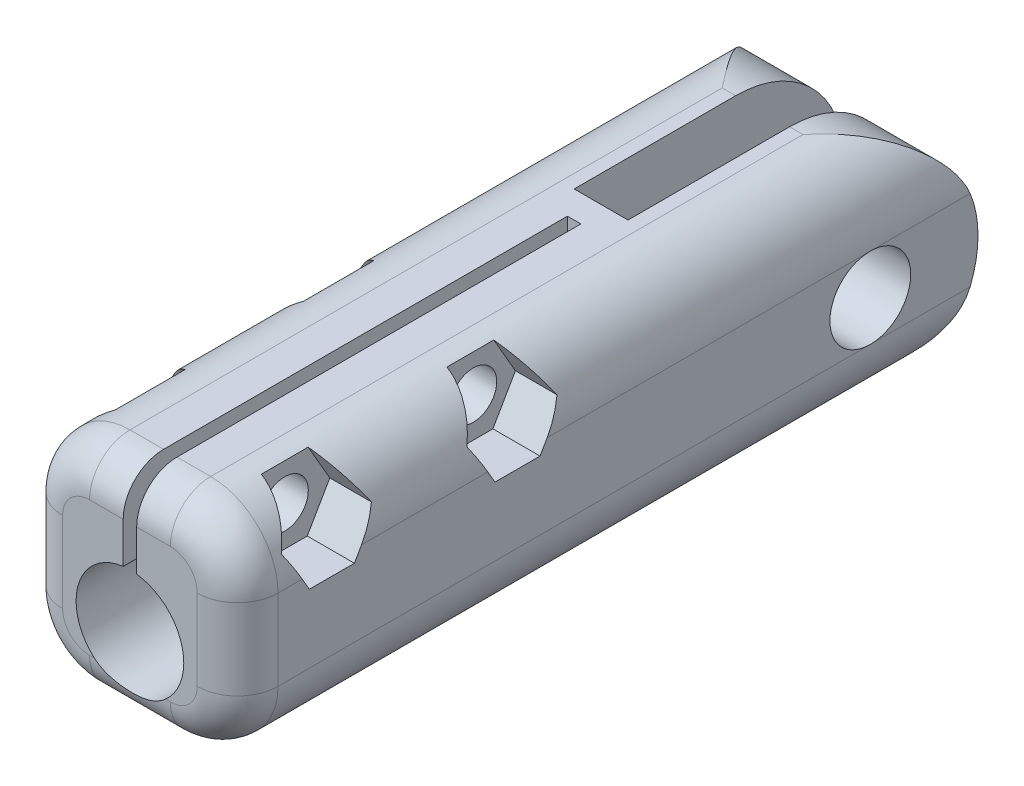
SolidWorks part; units mm, degrees
ref_plane "Front Plane" through (0, 0, 0) normal (0, 0, 1) x (1, 0, 0)
ref_plane "Top Plane" through (0, 0, 0) normal (0, 1, 0) x (1, 0, 0)
ref_plane "Right Plane" through (0, 0, 0) normal (1, 0, 0) x (0, 0, -1)
sketch "Sketch1" plane through (0, 0, 0) normal (0, 0, 1) x (1, 0, 0)
  line L1 (-8, -8) -> (8, -8)
  line L2 (-8, -8) -> (-8, 8)
  line L3 (-8, 8) -> (8, 8)
  line L4 (8, -8) -> (8, 8)
  line L5 (-8, -8) -> (8, 8) construction
  line L6 (-8, 8) -> (8, -8) construction
  point P0 (0, 0)
  dimension "D1" = 16
  dimension "D2" = 16
extrude "Boss-Extrude1" add sketch "Sketch1" along normal blind 55
sketch "Sketch2" plane through (0, 8, 0) normal (0, 1, 0) x (1, 0, 0)
  line L0 (0, 0) -> (0, -55) construction
  line L1 (8, 0) -> (-8, 0) construction
  line L2 (8, -55) -> (-8, -55) construction
  line L4 (2, -17) -> (-2, -17)
  line L5 (2, -17) -> (2, 0)
  line L6 (2, 0) -> (-2, 0)
  line L7 (-2, -17) -> (-2, 0)
  line L8 (2, -17) -> (-2, 0) construction
  line L9 (2, 0) -> (-2, -17) construction
  point P6 (0, -8.5)
  dimension "D1" = 4
  dimension "D2" = 17
extrude "Cut-Extrude1" cut sketch "Sketch2" against normal blind 17
sketch "Sketch3" plane through (8, 0, 0) normal (1, 0, 0) x (0, 0, -1)
  line L0 (0, -8) -> (0, 8) construction
  circle A0 centre (-8, 0) radius 3
  dimension "D1" = 6
  dimension "D2" = 8
extrude "Cut-Extrude2" cut sketch "Sketch3" against normal blind 45
sketch "Sketch4" plane through (0, 0, 55) normal (0, 0, 1) x (1, 0, 0)
  line L0 (8, 8) -> (-8, 8) construction
  line L1 (0.5, 0.4246) -> (-0.5, 0.4246)
  line L2 (0.5, 0.4246) -> (0.5, 8)
  line L3 (0.5, 8) -> (-0.5, 8)
  line L4 (-0.5, 0.4246) -> (-0.5, 8)
  line L5 (0.5, 0.4246) -> (-0.5, 8) construction
  line L6 (0.5, 8) -> (-0.5, 0.4246) construction
  line L7 (-8, -8) -> (8, -8) construction
  line L8 (0, 8) -> (0, -8) construction
  circle A0 centre (0, -2) radius 4
  point P3 (0, 4.2123)
  line M3 (8, 8) -> (-8, 8)
  dimension "D1" = 8
  dimension "D2" = 1
  dimension "D3" = 6
extrude "Cut-Extrude3" cut sketch "Sketch4" against normal blind 33 contours L4 A0 L2 L1 | A0 L2 L4 M3 | L2 A0 L4 L1 region at (0, -2.1031, 55) region at (0, 1.2071, 55) region at (0, 4.9948, 55)
fillet "Fillet1" radius 5 4 edges at (8, 8, 27.5) (-8, 8, 27.5) (8, -8, 27.5) (-8, -8, 27.5)
fillet "Fillet2" radius 3 9 edges at (-1.75, 8, 55) (1.75, 8, 55) (6.5355, 6.5355, 55) (8, 0, 55) (6.5355, -6.5355, 55) (0, -8, 55) (-6.5355, -6.5355, 55) (-8, 0, 55) (-6.5355, 6.5355, 55)
sketch "Sketch5" plane through (0.5, 0, 0) normal (-1, 0, 0) x (0, 0, 1)
  line L0 (52, 8) -> (52, 1.9686) construction
  line L1 (22, 1.9686) -> (55, 1.9686) construction
  line L2 (52, 4.9843) -> (22, 4.9843) construction
  line L3 (22, 1.9686) -> (22, 8) construction
  circle A0 centre (48, 4.9843) radius 1.75
  circle A1 centre (34, 4.9843) radius 1.75
  dimension "D1" = 3.5
  dimension "D2" = 3.5
  dimension "D3" = 4
  dimension "D4" = 14
extrude "Cut-Extrude4" cut sketch "Sketch5" against normal blind 40 and the other way blind 40 contours A0 | A1 region at (0.5, 4.9843, 48)
sketch "Sketch6" plane through (0.5, 0, 0) normal (-1, 0, 0) x (0, 0, 1)
  line L0 (22, 8) -> (52, 8) construction
  line L1 (49.6743, 7.8843) -> (46.3257, 7.8843)
  line L2 (46.3257, 7.8843) -> (44.6514, 4.9843)
  line L3 (44.6514, 4.9843) -> (46.3257, 2.0843)
  line L4 (46.3257, 2.0843) -> (49.6743, 2.0843)
  line L5 (49.6743, 2.0843) -> (51.3486, 4.9843)
  line L6 (51.3486, 4.9843) -> (49.6743, 7.8843)
  line L7 (35.8851, 7.8843) -> (32.5365, 7.8843)
  line L8 (32.5365, 7.8843) -> (30.8621, 4.9843)
  line L9 (30.8621, 4.9843) -> (32.5365, 2.0843)
  line L10 (32.5365, 2.0843) -> (35.8851, 2.0843)
  line L11 (35.8851, 2.0843) -> (37.5594, 4.9843)
  line L12 (37.5594, 4.9843) -> (35.8851, 7.8843)
  circle A0 centre (48, 4.9843) radius 2.9 construction
  circle A1 centre (34.2108, 4.9843) radius 2.9 construction
  dimension "D1" = 5.8
  dimension "D2" = 5.8
extrude "Cut-Extrude5" cut sketch "Sketch6" against normal blind 40 from offset 4 offset against normal yes
sketch "Sketch7" plane through (-0.5, 0, 0) normal (1, 0, 0) x (0, 0, -1)
  circle A0 centre (-48, 4.9843) radius 3.5
  circle A1 centre (-34, 4.9843) radius 3.5
extrude "Cut-Extrude6" cut sketch "Sketch7" against normal blind 40 from offset 5 offset against normal yes
sketch "Sketch8" plane through (-8, 0, 0) normal (-1, 0, 0) x (0, 0, 1)
  line L0 (8, 8) -> (8, -8) construction
  line L1 (8, 8) -> (8.2684, 14.014)
  line L2 (8, -8) -> (7.7316, -14.014)
  arc A0 (8, 8) -> (8, -8) centre (8, 0) ccw
  arc A6 (8.2684, 14.014) -> (7.7316, -14.014) centre (8, 0) ccw
  dimension "D1" = 8
  dimension "D2" = 0
extrude "Cut-Extrude7" cut sketch "Sketch8" against normal through all
fillet "Fillet3" [suppressed] radius 5
chamfer "Chamfer1" distance 3 distance2 16 1 edges at (0, 8, 17) first distance on face at (0, 8, 26.5)
